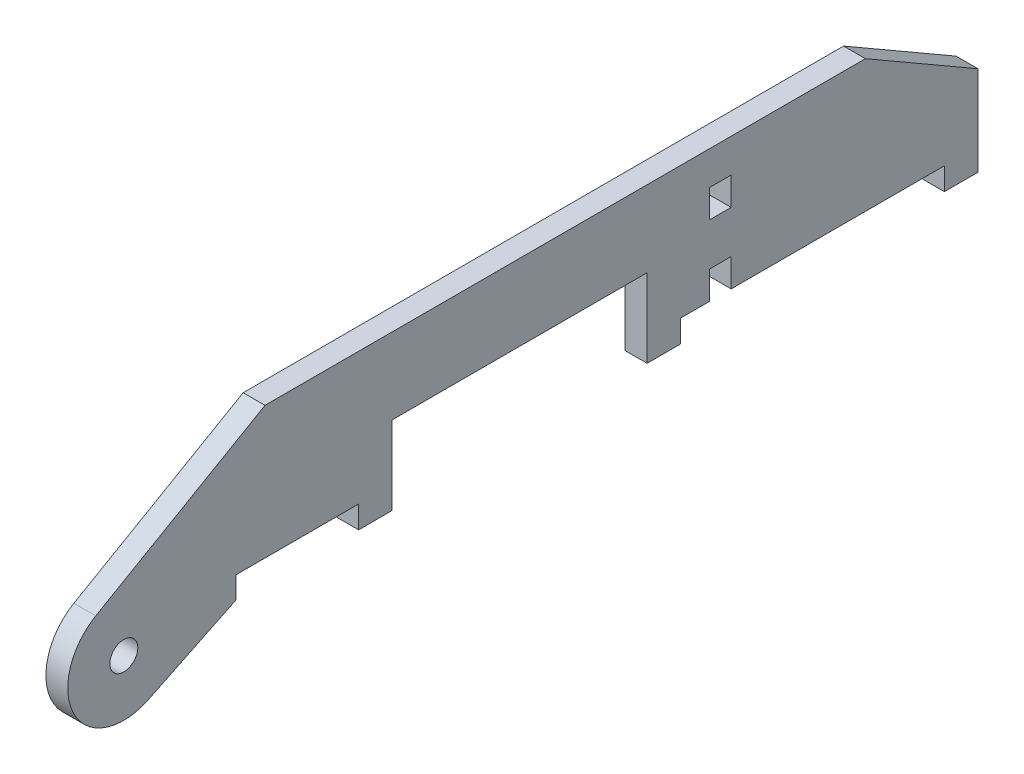
SolidWorks part; units mm, degrees
ref_plane "Front" through (0, 0, 0) normal (0, 0, 1) x (1, 0, 0)
ref_plane "Top" through (0, 0, 0) normal (0, 1, 0) x (1, 0, 0)
ref_plane "Right" through (0, 0, 0) normal (1, 0, 0) x (0, 0, -1)
ref_axis "side-side" through (80.9, 0, 0) along (-1, 0, 0)
ref_axis "up-down" through (0, 50, 0) along (0, -1, 0)
ref_axis "front-back" through (0, 0, -80.9) along (0, 0, 1)
sketch "Sketch1" plane through (0, 0, 0) normal (1, 0, 0) x (0, 0, -1)
  line L0 (-97.0573, 54.483) -> (-105.9473, 54.483) construction
  line L1 (-94.6424, 54.483) -> (-122.4573, 54.483)
  line L2 (-21.6519, 54.483) -> (-15.1765, 54.483)
  line L3 (45.72, 49.403) -> (45.72, 69.723)
  line L4 (-87.0224, 49.403) -> (-87.0224, 67.183)
  line L5 (-87.0224, 67.183) -> (-29.2719, 67.183)
  line L6 (-29.2719, 49.403) -> (-29.2719, 67.183)
  line L7 (20.2034, 84.455) -> (-115.8559, 84.455)
  line L8 (45.72, 69.723) -> (20.2034, 84.455)
  line L9 (-122.4573, 54.483) -> (-122.4573, 49.53)
  line L10 (-97.0573, 49.53) -> (-105.9473, 49.53) construction
  line L11 (-122.4573, 49.53) -> (-142.3098, 39.89)
  line L12 (-132.6173, 54.483) -> (-132.6173, 49.53) construction
  line L13 (-154.2073, 62.3128) -> (-115.8559, 84.455)
  line L14 (38.1, 54.483) -> (27.94, 54.483) construction
  line L16 (45.72, 54.483) -> (45.72, 49.53) construction
  line L17 (-87.0224, 49.403) -> (-94.6424, 49.403)
  line L18 (-94.6424, 54.483) -> (-94.6424, 49.403)
  line L19 (-10.2235, 54.483) -> (38.1, 54.483)
  line L21 (-29.2719, 49.403) -> (-21.6519, 49.403)
  line L22 (-21.6519, 54.483) -> (-21.6519, 49.403)
  line L23 (-15.1765, 54.483) -> (-15.1765, 60.833)
  line L24 (-15.1765, 60.833) -> (-10.2235, 60.833)
  line L25 (45.72, 49.403) -> (38.1, 49.403)
  line L26 (38.1, 54.483) -> (38.1, 49.403)
  line L27 (-10.2235, 54.483) -> (-10.2235, 60.833)
  line L28 (-10.2235, 76.835) -> (-15.1765, 76.835)
  line L29 (-10.2235, 76.835) -> (-10.2235, 70.485)
  line L30 (-10.2235, 70.485) -> (-15.1765, 70.485)
  line L31 (-15.1765, 76.835) -> (-15.1765, 70.485)
  arc A0 (-154.2073, 62.3128) -> (-142.3098, 39.89) centre (-147.8573, 51.3143) ccw
  circle A1 centre (-147.8573, 51.3143) radius 12.7 construction
  circle A2 centre (-147.8573, 51.3143) radius 3.175 construction
  circle A3 centre (-147.8573, 51.3143) radius 3.175
  dimension "D1" = 12.7
  dimension "D2" = 17.272
  dimension "D3" = 10.16
  dimension "D4" = 30
  dimension "D5" = 30
  dimension "D6" = 15.24
  dimension "D7" = 5.08
  dimension "D8" = 5.08
extrude "Boss-Extrude1" add sketch "Sketch1" along normal mid plane 4.953
